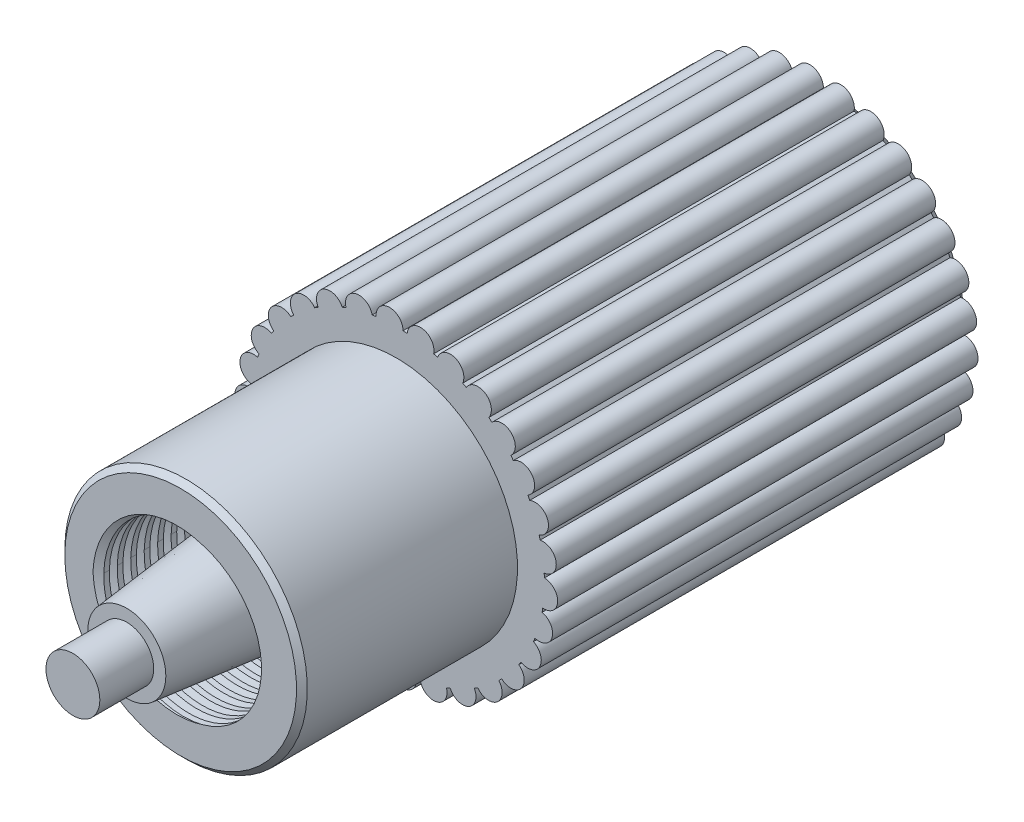
SolidWorks part; units mm, degrees
ref_plane "Front Plane" through (0, 0, 0) normal (0, 0, 1) x (1, 0, 0)
ref_plane "Top Plane" through (0, 0, 0) normal (0, 1, 0) x (1, 0, 0)
ref_plane "Right Plane" through (0, 0, 0) normal (1, 0, 0) x (0, 0, -1)
sketch "Sketch1" plane through (0, 0, 0) normal (0, 0, 1) x (1, 0, 0)
  circle A0 centre (0, 0) radius 1.25
  dimension "D1" = 2.5
extrude "Boss-Extrude1" add sketch "Sketch1" along normal blind 5 draft 6
sketch "Sketch2" plane through (0, 0, 0) normal (0, 0, -1) x (-1, 0, 0)
  circle A0 centre (0, 0) radius 1.5
  circle A1 centre (0, 0) radius 2.25
  dimension "D1" = 3
  dimension "D2" = 4.5
extrude "Boss-Extrude2" add sketch "Sketch2" against normal blind 4 separate body
sketch "Sketch3" plane through (0, 0, 0) normal (0, 0, -1) x (-1, 0, 0)
  circle A0 centre (0, 0) radius 2.75
  dimension "D1" = 5.5
extrude "Boss-Extrude3" add sketch "Sketch3" along normal blind 8
sketch "Sketch4" plane through (0, 0, 4) normal (0, 0, 1) x (1, 0, 0)
  circle A0 centre (0, 0) radius 1.5 construction
  circle A1 centre (0, 0) radius 1.5
curve "Helix/Spiral1" pitch 0.25 height 3.875 radius 1.5 centre (0, 0, 4) axis (0, 0, -1) start towards (-1, 0, 0)
ref_plane "Plane1" through (-1.5, 0, 4) normal (0, 0.9996, -0.0265) x (1, 0, 0)
sketch "Sketch5" plane through (-1.5, 0, 4) normal (0, 0.9996, -0.0265) x (1, 0, 0)
  line L1 (0.0635, -0.11) -> (0.0635, 0.11)
  line L2 (0.0635, 0.11) -> (-0.127, 0)
  line L3 (-0.127, 0) -> (0.0635, -0.11)
  circle A0 centre (0, 0) radius 0.0635 construction
  dimension "D1" = 0.22
sweep "Cut-Sweep1" cut profiles "Sketch5" path "Helix/Spiral1" align with end faces yes
chamfer "Chamfer1" distance 0.1 angle 45 1 edges at (-2.25, 0, 4)
sketch "Sketch6" plane through (0, 0, 5) normal (0, 0, 1) x (1, 0, 0)
  circle A0 centre (0, 0) radius 0.5
  dimension "D1" = 1
extrude "Boss-Extrude4" add sketch "Sketch6" along normal blind 1
chamfer "Chamfer2" distance 0.2 angle 45 1 edges at (-2.75, 0, -8)
sketch "Sketch7" plane through (0, 0, 0) normal (0, 0, 1) x (1, 0, 0)
  circle A0 centre (0, 0) radius 2.75 construction
  arc A1 (-2.4423, -1.264) -> (-2.1733, -1.685) centre (0, 0) ccw
  arc A2 (-2.5736, 0.9692) -> (-2.7064, 0.4877) centre (-2.6509, 0.7314) ccw
  arc A3 (-2.3158, 1.483) -> (-2.5459, 1.0397) centre (-2.4409, 1.2666) ccw
  arc A4 (-1.9569, 1.9321) -> (-2.2741, 1.5463) centre (-2.1243, 1.7464) ccw
  arc A5 (-1.5124, 2.2968) -> (-1.9029, 1.9853) centre (-1.7147, 2.1499) ccw
  arc A6 (-1.0018, 2.561) -> (-1.4485, 2.3376) centre (-1.2303, 2.4595) ccw
  arc A7 (-0.4475, 2.7133) -> (-0.9309, 2.5877) centre (-0.692, 2.6615) ccw
  arc A8 (0.1264, 2.7471) -> (-0.3725, 2.7246) centre (-0.1236, 2.7472) ccw
  arc A9 (0.6948, 2.6608) -> (0.2021, 2.7426) centre (0.4503, 2.7129) ccw
  arc A10 (1.2329, 2.4582) -> (0.7679, 2.6406) centre (1.0045, 2.56) ccw
  arc A11 (1.717, 2.1481) -> (1.3001, 2.4233) centre (1.5148, 2.2952) ccw
  arc A12 (2.1261, 1.7442) -> (1.7755, 2.1) centre (1.9589, 1.9301) ccw
  arc A13 (2.4423, 1.264) -> (2.1733, 1.685) centre (2.3174, 1.4806) ccw
  arc A14 (2.6517, 0.7286) -> (2.4762, 1.1963) centre (2.5746, 0.9665) ccw
  arc A15 (2.7453, 0.1614) -> (2.6708, 0.6553) centre (2.7193, 0.41) ccw
  arc A16 (2.7188, -0.4129) -> (2.7487, 0.0857) centre (2.7451, -0.1643) ccw
  arc A17 (2.5736, -0.9692) -> (2.7064, -0.4877) centre (2.6509, -0.7314) ccw
  arc A18 (2.3158, -1.483) -> (2.5459, -1.0397) centre (2.4409, -1.2666) ccw
  arc A19 (1.9569, -1.9321) -> (2.2741, -1.5463) centre (2.1243, -1.7464) ccw
  arc A20 (1.5124, -2.2968) -> (1.9029, -1.9853) centre (1.7147, -2.1499) ccw
  arc A21 (1.0018, -2.561) -> (1.4485, -2.3376) centre (1.2303, -2.4595) ccw
  arc A22 (0.4475, -2.7133) -> (0.9309, -2.5877) centre (0.692, -2.6615) ccw
  arc A23 (-0.1264, -2.7471) -> (0.3725, -2.7246) centre (0.1236, -2.7472) ccw
  arc A24 (-0.6948, -2.6608) -> (-0.2021, -2.7426) centre (-0.4503, -2.7129) ccw
  arc A25 (-1.2329, -2.4582) -> (-0.7679, -2.6406) centre (-1.0045, -2.56) ccw
  arc A26 (-1.717, -2.1481) -> (-1.3001, -2.4233) centre (-1.5148, -2.2952) ccw
  arc A27 (-2.1261, -1.7442) -> (-1.7755, -2.1) centre (-1.9589, -1.9301) ccw
  arc A28 (-2.4423, -1.264) -> (-2.1733, -1.685) centre (-2.3174, -1.4806) ccw
  arc A29 (-2.6517, -0.7286) -> (-2.4762, -1.1963) centre (-2.5746, -0.9665) ccw
  arc A30 (-2.7453, -0.1614) -> (-2.6708, -0.6553) centre (-2.7193, -0.41) ccw
  arc A31 (-2.7188, 0.4129) -> (-2.7487, -0.0857) centre (-2.7451, 0.1643) ccw
  arc A32 (-2.6517, -0.7286) -> (-2.4762, -1.1963) centre (0, 0) ccw
  arc A33 (-2.1261, -1.7442) -> (-1.7755, -2.1) centre (0, 0) ccw
  arc A34 (-1.717, -2.1481) -> (-1.3001, -2.4233) centre (0, 0) ccw
  arc A35 (-1.2329, -2.4582) -> (-0.7679, -2.6406) centre (0, 0) ccw
  arc A36 (-0.6948, -2.6608) -> (-0.2021, -2.7426) centre (0, 0) ccw
  arc A37 (-0.1264, -2.7471) -> (0.3725, -2.7246) centre (0, 0) ccw
  arc A38 (0.4475, -2.7133) -> (0.9309, -2.5877) centre (0, 0) ccw
  arc A39 (1.0018, -2.561) -> (1.4485, -2.3376) centre (0, 0) ccw
  arc A40 (1.5124, -2.2968) -> (1.9029, -1.9853) centre (0, 0) ccw
  arc A41 (1.9569, -1.9321) -> (2.2741, -1.5463) centre (0, 0) ccw
  arc A42 (2.3158, -1.483) -> (2.5459, -1.0397) centre (0, 0) ccw
  arc A43 (2.5736, -0.9692) -> (2.7064, -0.4877) centre (0, 0) ccw
  arc A44 (2.7188, -0.4129) -> (2.7487, 0.0857) centre (0, 0) ccw
  arc A45 (2.7453, 0.1614) -> (2.6708, 0.6553) centre (0, 0) ccw
  arc A46 (2.6517, 0.7286) -> (2.4762, 1.1963) centre (0, 0) ccw
  arc A47 (2.4423, 1.264) -> (2.1733, 1.685) centre (0, 0) ccw
  arc A48 (2.1261, 1.7442) -> (1.7755, 2.1) centre (0, 0) ccw
  arc A49 (1.717, 2.1481) -> (1.3001, 2.4233) centre (0, 0) ccw
  arc A50 (1.2329, 2.4582) -> (0.7679, 2.6406) centre (0, 0) ccw
  arc A51 (0.6948, 2.6608) -> (0.2021, 2.7426) centre (0, 0) ccw
  arc A52 (0.1264, 2.7471) -> (-0.3725, 2.7246) centre (0, 0) ccw
  arc A53 (-0.4475, 2.7133) -> (-0.9309, 2.5877) centre (0, 0) ccw
  arc A54 (-1.0018, 2.561) -> (-1.4485, 2.3376) centre (0, 0) ccw
  arc A55 (-1.5124, 2.2968) -> (-1.9029, 1.9853) centre (0, 0) ccw
  arc A56 (-1.9569, 1.9321) -> (-2.2741, 1.5463) centre (0, 0) ccw
  arc A57 (-2.3158, 1.483) -> (-2.5459, 1.0397) centre (0, 0) ccw
  arc A58 (-2.5736, 0.9692) -> (-2.7064, 0.4877) centre (0, 0) ccw
  arc A59 (-2.7188, 0.4129) -> (-2.7487, -0.0857) centre (0, 0) ccw
  arc A60 (-2.7453, -0.1614) -> (-2.6708, -0.6553) centre (0, 0) ccw
  point P96 (0, 0)
  dimension "D1" = 0.5
  dimension "D2" = 30
extrude "Boss-Extrude5" add sketch "Sketch7" against normal blind 7.8
sketch "Sketch8" plane through (0, 0, -8) normal (0, 0, -1) x (-1, 0, 0)
  spline S0 degree 2 poles (-2.1428, 0.3403) (-1.9478, 0.6684) (-1.6736, 1.1458) knots 0 0 0 1 1 1
  spline S1 degree 2 poles (-1.6736, 1.1458) (-1.6619, 0.7618) (-1.5182, 0.329) knots 0 0 0 1 1 1
  spline S2 degree 3 poles (-2.1428, 0.3403) (-2.0889, 0.3807) (-2.0306, 0.4076) (-1.9679, 0.421) knots 0 0 0 0 0.324056 0.324056 0.324056 0.324056
  spline S3 degree 3 poles (-1.9679, 0.421) (-2.0222, -2.8441) (1.5456, -2.564) (2.1643, -0.6385) knots 0 0 0 0 1 1 1 1
  spline S4 degree 3 poles (-1.6813, 0.3989) (-1.3488, -1.5559) (0.6082, -1.8093) (1.4748, -0.0781) knots 0 0 0 0 1 1 1 1
  spline S5 degree 2 poles (2.1643, -0.6385) (1.3462, -0.9366) (1.4748, -0.0781) knots 0 0 0 1 1 1
  spline S6 degree 2 poles (-1.6813, 0.3989) (-1.6029, 0.3738) (-1.5182, 0.329) knots 0.774029 0.774029 0.774029 1 1 1
extrude "Boss-Extrude6" add sketch "Sketch8" along normal blind 0.1
